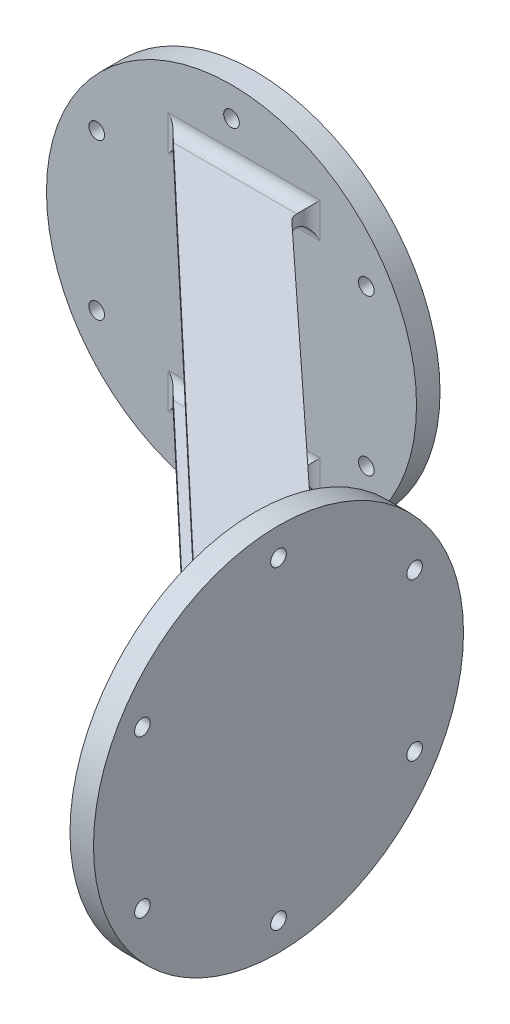
SolidWorks part; units mm, degrees
material "PETG"
ref_plane "Front Plane" through (0, 0, 0) normal (0, 0, 1) x (1, 0, 0)
ref_plane "Top Plane" through (0, 0, 0) normal (0, 1, 0) x (1, 0, 0)
ref_plane "Right Plane" through (0, 0, 0) normal (1, 0, 0) x (0, 0, -1)
other "Center of Mass"
sketch "Sketch1" plane through (0, 0, 0) normal (0, 0, 1) x (1, 0, 0)
  circle A0 centre (0, 0) radius 31.5
extrude "Boss-Extrude1" add sketch "Sketch1" along normal blind 4
ref_plane "Plane1" through (65, 0, 0) normal (1, 0, 0) x (0, 0, -1)
sketch "Sketch2" plane through (65, 0, 0) normal (1, 0, 0) x (0, 0, -1)
  circle A0 centre (-65, 0) radius 31.5
  dimension "D1" = 65
extrude "Boss-Extrude2" add sketch "Sketch2" along normal blind 4 separate body
sketch "Sketch4" plane through (65, 0, 0) normal (-1, 0, 0) x (0, 0, 1)
  line L0 (65, 45.1153) -> (65, -45.9192) construction
  line L1 (25.8542, 0) -> (115.6659, 0) construction
  line L2 (50, 30.7128) -> (50, -40.4843) construction
  line L3 (80, -37.4951) -> (80, 30.7128) construction
  circle A0 centre (50, 10) radius 3
  circle A1 centre (80, 10) radius 3
  circle A2 centre (80, -10) radius 3
  circle A3 centre (50, -10) radius 3
  dimension "D1" = 15
  dimension "D2" = 15
  dimension "D3" = 10
  dimension "D4" = 10
sketch3d "3DSketch4"
  line L0 (75.6872, 0, 4) -> (-75.6872, 0, 4) construction
  line L1 (0, 0, 4) -> (39.6369, 0, 4) construction
  line L2 (0, -37.2332, 4) -> (0, 37.3953, 4) construction
  line L3 (65, 36.8663, 65) -> (65, -39.5144, 65) construction
  line L4 (65, 0, 20.8162) -> (65, 0, 99.0996) construction
  line L5 (65, -36.5145, 55) -> (65, 36.8663, 55) construction
  circle A2 centre (-10, 20, 4) radius 3
  circle A3 centre (10, 20, 4) radius 3
  circle A4 centre (10, -20, 4) radius 3
  circle A5 centre (-10, -20, 4) radius 3
  circle A6 centre (65, 18.3549, 55) radius 2.3835
  point P8 (-10, 20, 7)
  point P12 (10, 20, 7)
  point P15 (10, -20, 7)
  point P18 (-10, -20, 7)
  point P27 (62.6165, 18.3549, 55)
  point P28 (0, 0, 0)
  dimension "D2" = 20
  dimension "D1" = 10
  dimension "D3" = 10
sketch "Sketch5" plane through (0, 0, 4) normal (0, 0, 1) x (1, 0, 0)
  line L0 (0, 33.8161) -> (0, -38.4037) construction
  line L1 (-39.4908, 0) -> (42.4546, 0) construction
  line L2 (-14.7291, 14.7291) -> (0, 0) construction
  line L3 (0, 0) -> (15.1762, -15.1762) construction
  line L4 (0, 0) -> (-11.8125, -11.8125) construction
  line L5 (0, 0) -> (10.6507, 10.6507) construction
  circle A0 centre (0, 0) radius 26.5 construction
  circle A1 centre (0, 26.5) radius 1.33
  circle A2 centre (22.9497, 13.25) radius 1.33
  circle A3 centre (22.9497, -13.25) radius 1.33
  circle A4 centre (0, -26.5) radius 1.33
  circle A5 centre (-22.9497, -13.25) radius 1.33
  circle A6 centre (-22.9497, 13.25) radius 1.33
  circle A7 centre (0, 0) radius 8.25 construction
  circle A8 centre (0, 8.25) radius 1.33
  circle A9 centre (8.25, 0) radius 1.33
  circle A10 centre (0, -8.25) radius 1.33
  circle A11 centre (-8.25, 0) radius 1.33
  circle A12 centre (-5.8336, 5.8336) radius 1.33
  circle A14 centre (5.8336, 5.8336) radius 1.33
  circle A15 centre (5.8336, -5.8336) radius 1.33
  circle A16 centre (-5.8336, -5.8336) radius 1.33
  dimension "D1" = 6
  dimension "D2" = 4
  dimension "D3" = 45
  dimension "D5" = 4
  dimension "D4" = 45
sketch "Body-faced i-beam" plane through (0, 0, 4) normal (0, 0, 1) x (1, 0, 0)
  line L0 (0, 33.8161) -> (0, -38.4037) construction
  line L1 (-10, 20) -> (10, 20)
  line L2 (-10, 20) -> (-10, 18)
  line L3 (-10, 18) -> (-1.5, 18)
  line L4 (10, 20) -> (10, 18)
  line L6 (-1.5, 18) -> (-1.5, -18)
  line L8 (1.5, 18) -> (1.5, -18)
  line L9 (-39.4908, 0) -> (42.4546, 0) construction
  line L10 (1.5, -18) -> (10, -18)
  line L11 (-10, -18) -> (-1.5, -18)
  line L12 (-10, -18) -> (-10, -20)
  line L13 (-10, -20) -> (10, -20)
  line L14 (10, -18) -> (10, -20)
  line L15 (1.5, 18) -> (10, 18)
  dimension "D1" = 10
  dimension "D2" = 10
  dimension "D3" = 1.5
  dimension "D4" = 1.5
  dimension "D5" = 20
  dimension "D6" = 20
sketch "Leg-faced i-beam" plane through (65, 0, 0) normal (-1, 0, 0) x (0, 0, 1)
  line L0 (27.4532, 0) -> (108.9123, 0) construction
  line L1 (65, -33.9896) -> (65, 37.3469) construction
  line L2 (66.5, 18) -> (75, 18)
  line L3 (55, 20) -> (75, 20)
  line L4 (55, 20) -> (55, 18)
  line L5 (55, 18) -> (63.5, 18)
  line L6 (75, 20) -> (75, 18)
  line L7 (55, -18) -> (63.5, -18)
  line L8 (55, -18) -> (55, -20)
  line L9 (55, -20) -> (75, -20)
  line L10 (75, -18) -> (75, -20)
  line L12 (63.5, 18) -> (63.5, -18)
  line L14 (66.5, 18) -> (66.5, -18)
  line L15 (66.5, -18) -> (75, -18)
  dimension "D1" = 1.5
  dimension "D2" = 1.5
  dimension "D3" = 20
  dimension "D4" = 20
  dimension "D5" = 10
  dimension "D6" = 10
  dimension "D7" = 10
  dimension "D8" = 10
loft "Loft1" add profiles "Body-faced i-beam", "Leg-faced i-beam" connector at (-1.5, 18, 4) connector at (65, 18, 66.5)
extrude "Cut-Extrude1" cut sketch "Sketch5" against normal through all contours A6 | A5 | A4 | A3 | A2 | A1
sketch "Sketch6" plane through (65, 0, 0) normal (-1, 0, 0) x (0, 0, 1)
  circle A0 centre (65, 0) radius 26.75 construction
  circle A1 centre (65, 26.75) radius 1.33
  circle A2 centre (41.8338, 13.375) radius 1.33
  circle A3 centre (41.8338, -13.375) radius 1.33
  circle A4 centre (65, -26.75) radius 1.33
  circle A5 centre (88.1662, -13.375) radius 1.33
  circle A6 centre (88.1662, 13.375) radius 1.33
  dimension "D1" = 6
extrude "Cut-Extrude2" cut sketch "Sketch6" against normal through all
sketch "Sketch7" plane through (-2.6997, 0, 2.8725) normal (-0.6849, 0, 0.7287) x (0.7287, 0, 0.6849)
  line L0 (47.0904, 24.9116) -> (47.0904, -23.0504) construction
  line L1 (1.6464, 0) -> (92.907, 0) construction
  line L2 (1.6464, 18) -> (1.6464, -18) construction
  line L3 (92.907, -18) -> (92.907, 18) construction
  circle A0 centre (47.0904, 0) radius 6
extrude "Cut-Extrude3" cut sketch "Sketch7" against normal blind 10
fillet "Fillet1" radius 2 20 edges
sketch "Sketch8" plane through (65, 0, 0) normal (-1, 0, 0) x (0, 0, 1)
  line L0 (65, 36.8663) -> (65, -39.5144) construction
  circle A0 centre (65, 0) radius 18.5187
  circle A1 centre (65, 0) radius 23.2857
  circle A2 centre (65, 0) radius 20.9022 construction
